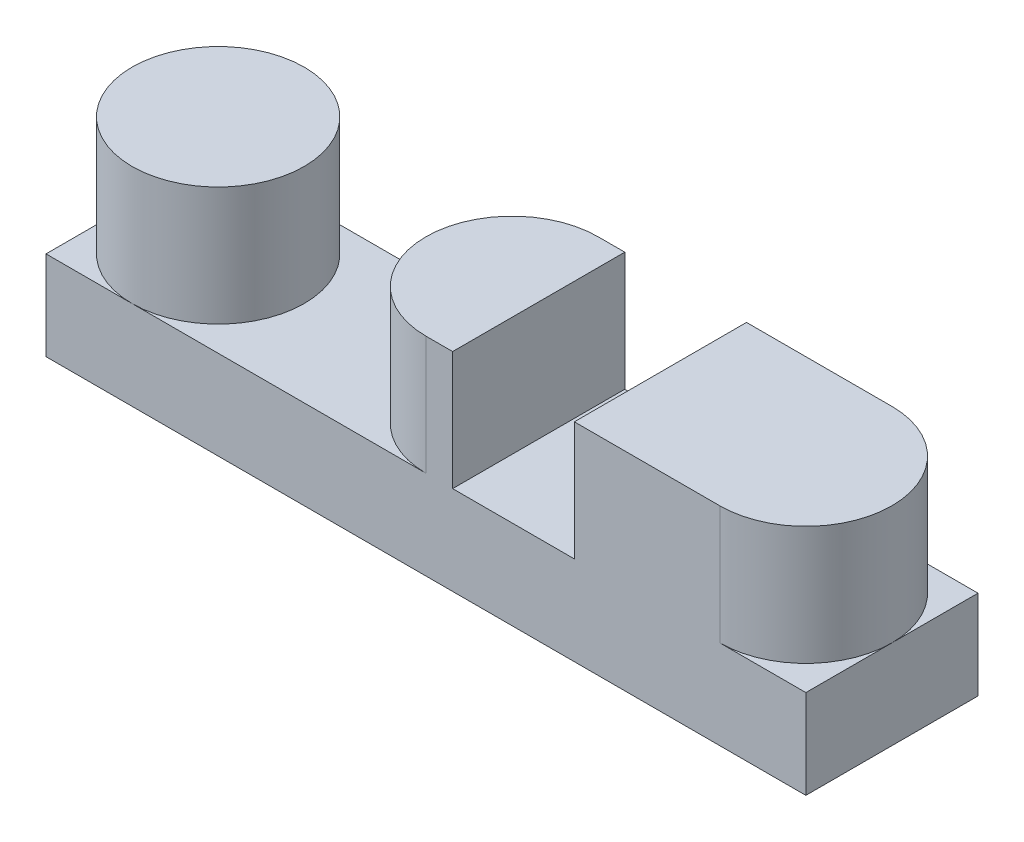
SolidWorks part; units mm, degrees
ref_plane "Front Plane" through (0, 0, 0) normal (0, 0, 1) x (1, 0, 0)
ref_plane "Top Plane" through (0, 0, 0) normal (0, 1, 0) x (1, 0, 0)
ref_plane "Right Plane" through (0, 0, 0) normal (1, 0, 0) x (0, 0, -1)
sketch "Sketch1" plane through (0, 0, 0) normal (0, 1, 0) x (1, 0, 0)
  line L0 (5.8, 1.1139) -> (5.8, 4.753) construction
  line L1 (0, 0) -> (25.6, 0)
  line L2 (0, 0) -> (0, 5.8)
  line L3 (0, 5.8) -> (25.6, 5.8)
  line L4 (25.6, 0) -> (25.6, 5.8)
  line L6 (25.6, 2.9) -> (0, 2.9) construction
  line L7 (15.8, 0) -> (17.8, 0)
  line L8 (15.8, 0) -> (15.8, 5.8)
  line L9 (15.8, 5.8) -> (17.8, 5.8)
  line L10 (17.8, 0) -> (17.8, 5.8)
  line L11 (15.8, 0) -> (17.8, 5.8) construction
  line L12 (15.8, 5.8) -> (17.8, 0) construction
  line L13 (12.8, 0) -> (13.7, 0)
  line L14 (12.8, 0) -> (12.8, 5.8)
  line L15 (12.8, 5.8) -> (13.7, 5.8)
  line L16 (13.7, 0) -> (13.7, 5.8)
  line L17 (22.7, 0) -> (17.8, 0)
  line L18 (22.7, 0) -> (22.7, 5.8)
  line L19 (22.7, 5.8) -> (17.8, 5.8)
  line L20 (17.8, 0) -> (17.8, 5.8)
  line L21 (9.9, 4.3559) -> (9.9, 0.8795) construction
  circle A0 centre (2.9, 2.9) radius 2.9
  circle A1 centre (12.8, 2.9) radius 2.9
  circle A2 centre (22.7, 2.9) radius 2.9
  point P9 (16.8, 2.9)
  point P12 (6.588, 0.8795)
  point P29 (6.907, 4.3559)
  point P30 (5.8, 1.1139)
  dimension "D3" = 5.8
  dimension "D1" = 0.9
  dimension "D2" = 4.9
  dimension "D4" = 2.1
  dimension "D5" = 2
  dimension "D6" = 4.1
extrude "Boss-Extrude1" add sketch "Sketch1" against normal blind 3 contours L1 L4 L3 L2
extrude "Boss-Extrude2" add sketch "Sketch1<4>" along normal blind 4 contours A0 | L14 A1 | A1 L16 L3 | A1 L1 L16 | L14 A1 L16 | L18 A2 | A2 L3 L10 L1 | L18 A2 region at (13.4761, 0, -0.0428) region at (11.5692, 0, -2.9) region at (13.2463, 0, -2.9) region at (2.9, 0, -2.9) region at (13.4761, 0, -5.7572) region at (19.1911, 0, -2.9) region at (21.4692, 0, -2.9) region at (23.9308, 0, -2.9)
sketch "Sketch1<4>" plane through (0, 0, 0) normal (0, 1, 0) x (1, 0, 0) same geometry as "Sketch1"
